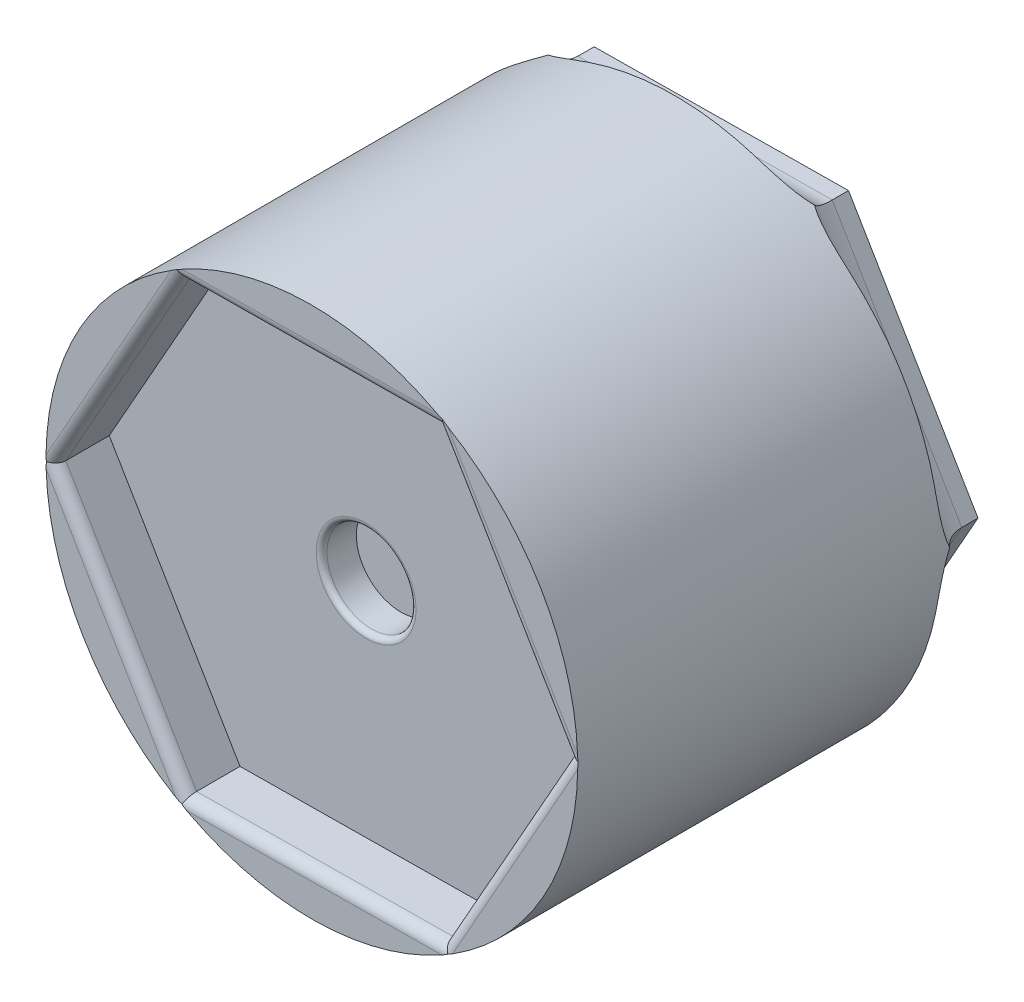
SolidWorks part; units mm, degrees
ref_plane "Front Plane" through (0, 0, 0) normal (1, 0, 0) x (0, 1, 0)
ref_plane "Top Plane" through (0, 0, 0) normal (0, 0, 1) x (0, 1, 0)
ref_plane "Right Plane" through (0, 0, 0) normal (0, 1, 0) x (-1, 0, 0)
sketch "Sketch1" plane through (0, 0, 0) normal (0, 0, 1) x (0, 1, 0)
  line L1 (20.1756, 11.9331) -> (-0.2466, 23.4391)
  line L2 (-0.2466, 23.4391) -> (-20.4222, 11.506)
  line L3 (-20.4222, 11.506) -> (-20.1756, -11.9331)
  line L4 (-20.1756, -11.9331) -> (0.2466, -23.4391)
  line L5 (0.2466, -23.4391) -> (20.4222, -11.506)
  line L6 (20.4222, -11.506) -> (20.1756, 11.9331)
  circle A0 centre (0, 0) radius 20.3 construction
extrude "HEX Feet" add sketch "Sketch1" along normal blind 4.5
sketch "Sketch3" plane through (0, 0, 4.5) normal (0, 0, 1) x (1, 0, 0)
  circle A0 centre (0, 0) radius 24.5
  dimension "D1" = 49
extrude "Circle Main Body" add sketch "Sketch3" along normal blind 33.45
sketch "Sketch4" plane through (0, 0, 37.95) normal (0, 0, 1) x (1, 0, 0)
  line L0 (11.6194, 20.6234) -> (-12.0507, 20.3744)
  line L7 (-12.0507, 20.3744) -> (-23.6701, -0.249)
  line L8 (-23.6701, -0.249) -> (-11.6194, -20.6234)
  line L9 (-11.6194, -20.6234) -> (12.0507, -20.3744)
  line L10 (12.0507, -20.3744) -> (23.6701, 0.249)
  line L11 (23.6701, 0.249) -> (11.6194, 20.6234)
extrude "TOP HEX Slot" cut sketch "Sketch4" against normal blind 5
fillet "Bottom hex chamf" radius 3 6 edges at (0.2136, -20.2989, 4.5) (17.6861, -9.9645, 4.5) (17.4726, 10.3344, 4.5) (-0.2136, 20.2989, 4.5) (-17.4726, -10.3344, 4.5) (-17.6861, 9.9645, 4.5)
fillet "Fillet2" radius 1 6 edges at (17.6447, 10.4362, 37.95) (17.8604, -10.0627, 37.95) (0.2157, -20.4989, 37.95) (-17.6447, -10.4362, 37.95) (-17.8604, 10.0627, 37.95) (-0.2157, 20.4989, 37.95)
sketch "Sketch5" plane through (0, 0, 32.95) normal (0, 0, 1) x (1, 0, 0)
  circle A0 centre (0, 0) radius 4.1
  dimension "D1" = 8.2
extrude "Cut-Extrude1" cut sketch "Sketch5" against normal blind 3.2
fillet "Fillet3" radius 0.5 1 edges at (4.1, 0, 32.95)
